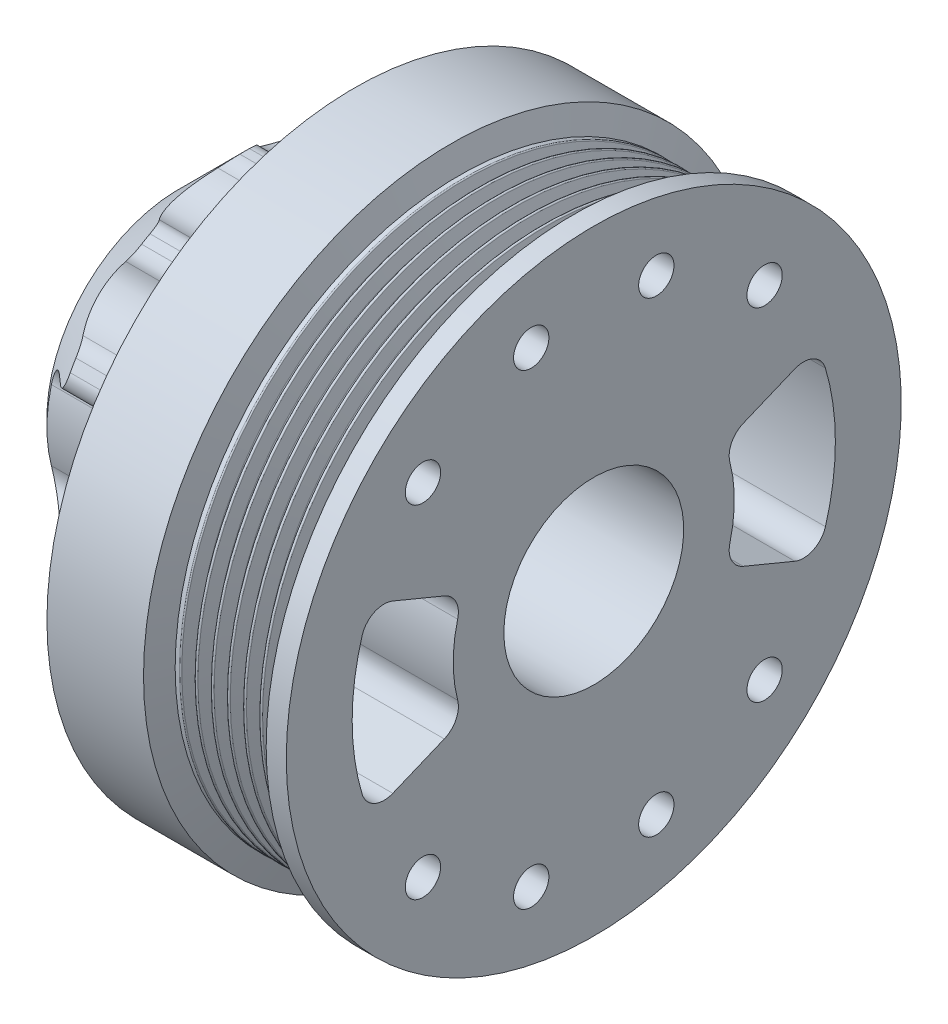
SolidWorks part; units mm, degrees
material "6061-T6 (SS)"
ref_plane "Front Plane" through (0, 0, 0) normal (0, 0, 1) x (1, 0, 0)
ref_plane "Top Plane" through (0, 0, 0) normal (0, 1, 0) x (1, 0, 0)
ref_plane "Right Plane" through (0, 0, 0) normal (1, 0, 0) x (0, 0, -1)
sketch "Sketch1" plane through (0, 0, 0) normal (0, 0, 1) x (1, 0, 0)
  line L0 (0, 0) -> (106.255, 0) construction
  line L1 (-19.05, 13) -> (40.95, 13)
  line L2 (40.95, 13) -> (40.95, 44.45)
  line L3 (40.95, 44.45) -> (6.35, 44.45)
  line L4 (6.35, 44.45) -> (6.35, 28.575)
  line L5 (6.35, 28.575) -> (-19.05, 28.575)
  line L6 (-19.05, 28.575) -> (-19.05, 13)
  dimension "D1" = 34.6
  dimension "D2" = 88.9
  dimension "D3" = 26
  dimension "D4" = 25.4
  dimension "D5" = 57.15
  dimension "D6" = 19.05
revolve "Revolve1" add sketch "Sketch1" angle 360 about L0
sketch "Sketch3" plane through (-19.05, 0, 0) normal (-1, 0, 0) x (0, 0, 1)
  line L0 (0, 0) -> (9.0393, 33.735) construction
  line L1 (0, 0) -> (0, 49.6351) construction
  arc A0 (2.2542, 28.4859) -> (12.2907, 25.7967) centre (8.2175, 30.6681) ccw
  circle A1 centre (0, 0) radius 28.575 construction
  arc A2 (12.2907, 25.7967) -> (2.2542, 28.4859) centre (0, 0) ccw
  point P6 (6.574, 24.5345)
  point P10 (7.3958, 27.6013)
  dimension "D1" = 34.925
  dimension "D2" = 3.175
  dimension "D3" = 6.35
  dimension "D4" = 15
extrude "Cut-Extrude1" cut sketch "Sketch3" against normal up to surface (25.4 mm away) up to face at (6.35, 0, 28.575)
fillet "Fillet1" radius 2.54 2 edges at (-6.35, 25.7967, 12.2907) (-6.35, 28.4859, 2.2542)
sketch "Sketch6" plane through (6.35, 0, 0) normal (-1, 0, 0) x (0, 0, 1)
  point P0 (9.0393, 33.735)
hole_wizard "1/4-20 Tapped Hole1" positions "Sketch7" profile "Sketch9" tap size "1/4-20" standard "ANSI Inch" end condition through all
sketch "Sketch7" plane through (6.35, 0, 0) normal (-1, 0, 0) x (0, 0, 1)
  point P0 (9.0393, 33.735)
sketch "Sketch9" plane through (6.35, 33.735, 9.0393) normal (0, 1, 0) x (0, 0, 1)
  line L0 (0, 0) -> (0, 34.6)
  line L1 (0, 34.6) -> (2.5527, 34.6)
  line L2 (2.5527, 34.6) -> (2.5527, 0)
  line L5 (2.5527, 0) -> (0, 0)
  line L11 (0, -6.35) -> (0, 107.95) construction
  dimension "Thru Tap Drill Dia." = 5.1054
  dimension "Thru Tap Drill Depth" = 34.6
pattern_circular "CirPattern1" count 12 over 360 about axis through (6.35, 0, 0) along (-1, 0, 0) skipping 3, 4, 9, 10 of "Cut-Extrude1", "Fillet1", "1/4-20 Tapped Hole1"
sketch "Sketch10" plane through (0, 0, 0) normal (0, 0, 1) x (1, 0, 0)
  line L0 (40.95, 44.45) -> (6.35, 44.45) construction
  line L2 (35.9966, 40.9635) -> (35.401, 39.3272)
  line L3 (34.6372, 39.3272) -> (34.0416, 40.9635)
  line L9 (36.1875, 44.45) -> (33.8507, 44.45)
  line L10 (40.95, 44.45) -> (6.35, 44.45) construction
  line L11 (34.0416, 40.9635) -> (35.9966, 40.9635) construction
  line L12 (0, 0) -> (72.0631, 0) construction
  line L13 (36.1875, 41.0972) -> (36.1875, 44.45)
  line L14 (33.8507, 41.0972) -> (33.8507, 44.45)
  line L15 (33.2905, 39.0598) -> (37.1262, 39.0598) construction
  line L16 (32.9874, 42.291) -> (37.178, 42.291) construction
  arc A0 (34.6372, 39.3272) -> (35.401, 39.3272) centre (35.0191, 39.4662) ccw
  arc A1 (35.9966, 40.9635) -> (36.1875, 41.0972) centre (36.1875, 40.894) cw
  arc A2 (34.0416, 40.9635) -> (33.8507, 41.0972) centre (33.8507, 40.894) ccw
  dimension "D4" = 4.7625
  dimension "D2" = 40
  dimension "D5" = 2.0374
  dimension "D6" = 2.3368
  dimension "D7" = 42.291
  dimension "D8" = 1.1938
ref_axis "Axis1" through (40.95, 0, 0) along (-1, 0, 0)
revolve "Cut-Revolve1" cut sketch "Sketch10" angle 360 about axis through (40.95, 0, 0) along (-1, 0, 0)
pattern_linear "LPattern2" count 6 spacing 2.3368 along (-1, 0, 0) of "Cut-Revolve1"
sketch "Sketch23" plane through (0, 0, 0) normal (0, 0, 1) x (1, 0, 0)
  line L0 (36.1875, 41.0972) -> (36.8225, 41.0972)
  line L1 (36.8225, 41.0972) -> (38.0428, 44.45)
  line L2 (40.95, 44.45) -> (36.1875, 44.45) construction
  line L3 (38.0428, 44.45) -> (36.1875, 44.45)
  line L4 (36.1875, 44.45) -> (36.1875, 41.0972)
  line L5 (35.0191, 39.0598) -> (35.0191, 41.518) construction
  line L6 (29.1771, 41.0972) -> (29.1771, 44.846) construction
  line L7 (22.1667, 44.45) -> (22.1667, 41.0972)
  line L8 (20.3114, 44.45) -> (22.1667, 44.45)
  line L9 (21.5317, 41.0972) -> (20.3114, 44.45)
  line L10 (22.1667, 41.0972) -> (21.5317, 41.0972)
  line L11 (40.95, 44.45) -> (36.1875, 44.45) construction
  arc A0 (34.6372, 39.3272) -> (35.401, 39.3272) centre (35.0191, 39.4662) ccw construction
  arc A1 (29.368, 40.9635) -> (28.9862, 40.9635) centre (29.1771, 40.894) ccw construction
  dimension "D1" = 1.8034
  dimension "D2" = 20
revolve "Cut-Revolve3" cut sketch "Sketch23" angle 360 about axis through (40.95, 0, 0) along (-1, 0, 0)
sketch "Sketch11" plane through (0, 0, 0) normal (0, 1, 0) x (1, 0, 0)
  line L1 (6.35, 44.45) -> (-19.05, 44.45)
  line L2 (-19.05, 44.45) -> (-19.05, 19.05)
  line L3 (-19.05, 13) -> (-19.05, -13) construction
  line L4 (0, 0) -> (-37.8551, 0) construction
  line L5 (-19.05, 19.05) -> (6.35, 44.45)
  line L11 (6.35, -6.4866) -> (6.35, -11.592) construction
  point P13 (-19.05, 28.575)
  dimension "D1" = 9.525
  dimension "D2" = 45
revolve "Cut-Revolve2" cut sketch "Sketch11" angle 360 about L4
sketch "Sketch25" plane through (-19.05, 0, 0) normal (-1, 0, 0) x (0, 0, 1)
  line L0 (18.7732, 7.7761) -> (32.2665, 13.3652)
  line L1 (18.7732, -7.7761) -> (32.2665, -13.3652)
  line L2 (0, 0) -> (34.925, 0) construction
  arc A0 (18.7732, 7.7761) -> (18.7732, -7.7761) centre (0, 0) cw
  arc A1 (32.2665, 13.3652) -> (32.2665, -13.3652) centre (0, 0) cw
  point P6 (32.0766, -13.8148)
  point P8 (32.4606, -12.8867)
  point P9 (31.7815, 14.4808)
  dimension "D1" = 20.32
  dimension "D2" = 34.925
  dimension "D3" = 45
extrude "Cut-Extrude2" cut sketch "Sketch25" against normal through all
fillet "Fillet2" radius 3.302 4 edges at (23.65, -13.3652, 32.2665) (23.65, 13.3652, 32.2665) (11.585, -7.7761, 18.7732) (11.585, 7.7761, 18.7732)
mirror "Mirror1" about plane through (0, 0, 0) normal (0, 0, 1) of "Fillet2", "Cut-Extrude2"
fillet "Fillet3" radius 2.54 4 edges at (-1.5875, 10.9352, -26.3999) (-1.5875, -10.9352, -26.3999) (-1.5875, -10.9352, 26.3999) (-1.5875, 10.9352, 26.3999)
equation "\"D7@Sketch10\"=3.33in/2"
equation "\"D8@Sketch10\"=.094/2"
